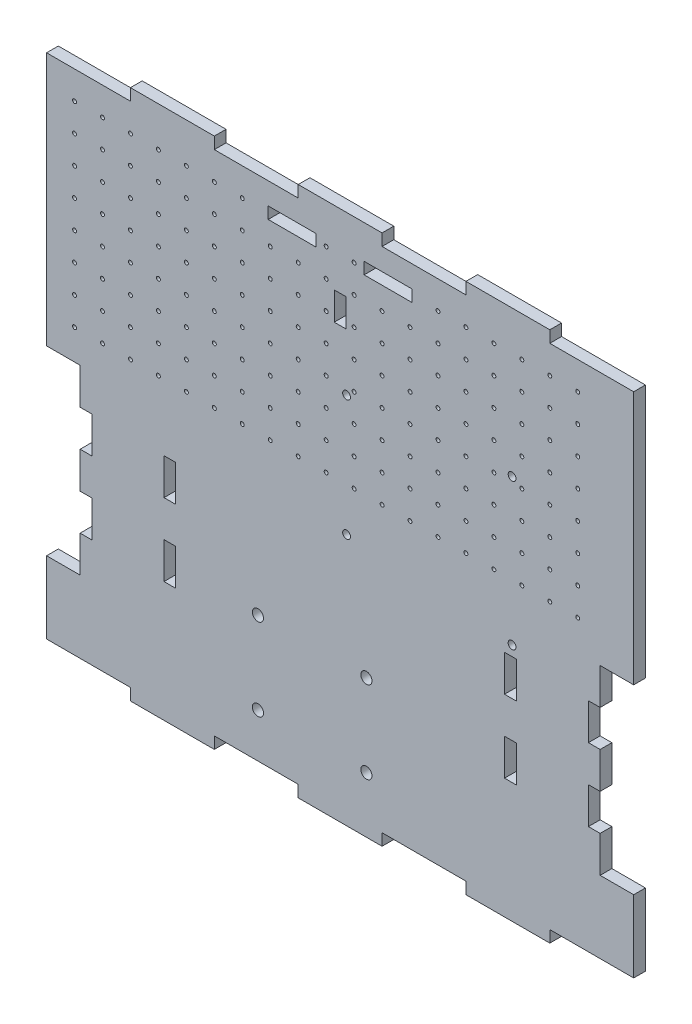
SolidWorks part; units mm, degrees
ref_plane "Front Plane" through (0, 0, 0) normal (0, 0, 1) x (1, 0, 0)
ref_plane "Top Plane" through (0, 0, 0) normal (0, 1, 0) x (1, 0, 0)
ref_plane "Right Plane" through (0, 0, 0) normal (1, 0, 0) x (0, 0, -1)
sketch "Sketch1" plane through (0, 0, 0) normal (0, 0, 1) x (1, 0, 0)
  line L1 (-133.35, 120.65) -> (133.35, 120.65)
  line L2 (-133.35, 120.65) -> (-133.35, -120.65)
  line L3 (-133.35, -120.65) -> (133.35, -120.65)
  line L4 (133.35, 120.65) -> (133.35, -120.65)
  line L5 (-133.35, 120.65) -> (133.35, -120.65) construction
  line L6 (-133.35, -120.65) -> (133.35, 120.65) construction
  point P0 (0, 0)
  dimension "D1" = 241.3
  dimension "D2" = 266.7
extrude "Boss-Extrude1" add sketch "Sketch1" along normal blind 5.334
sketch "Sketch2" plane through (0, 0, 0) normal (0, 0, -1) x (-1, 0, 0)
  line L0 (133.35, 120.65) -> (133.35, -120.65) construction
  line L1 (133.35, 0) -> (118.11, 0)
  line L2 (133.35, 0) -> (133.35, -82.55)
  line L3 (133.35, -82.55) -> (118.11, -82.55)
  line L4 (118.11, 0) -> (118.11, -82.55)
  line L5 (-133.35, -120.65) -> (-133.35, 120.65) construction
  line L6 (-133.35, 0) -> (-118.11, 0)
  line L7 (-133.35, 0) -> (-133.35, -82.55)
  line L8 (-133.35, -82.55) -> (-118.11, -82.55)
  line L9 (-118.11, 0) -> (-118.11, -82.55)
  line L10 (133.35, -120.65) -> (-133.35, -120.65) construction
  dimension "D1" = 82.55
  dimension "D2" = 82.55
  dimension "D3" = 38.1
  dimension "D4" = 38.1
  dimension "D5" = 15.24
  dimension "D6" = 15.24
extrude "Cut-Extrude1" cut sketch "Sketch2" against normal through all
sketch "Sketch9" plane through (0, 0, 5.334) normal (0, 0, 1) x (1, 0, 0)
  line L0 (-118.11, 0) -> (-118.11, -82.55) construction
  line L1 (-118.11, -16.51) -> (-112.776, -16.51)
  line L2 (-118.11, -16.51) -> (-118.11, -33.02)
  line L3 (-118.11, -33.02) -> (-112.776, -33.02)
  line L4 (-112.776, -16.51) -> (-112.776, -33.02)
  line L5 (-118.11, 0) -> (-112.776, 0) construction
  line L6 (-118.11, -49.53) -> (-112.776, -49.53)
  line L7 (-118.11, -49.53) -> (-118.11, -66.04)
  line L8 (-118.11, -66.04) -> (-112.776, -66.04)
  line L9 (-112.776, -49.53) -> (-112.776, -66.04)
  line L10 (-112.776, 0) -> (-112.776, -16.51) construction
  line L11 (-112.776, -33.02) -> (-112.776, -49.53) construction
  line L12 (-118.11, -82.55) -> (-112.776, -82.55) construction
  line L13 (-112.776, -82.55) -> (-112.776, -66.04) construction
  line L14 (0, -120.65) -> (0, 120.65) construction
  line L15 (-133.35, -120.65) -> (133.35, -120.65) construction
  line L16 (133.35, 120.65) -> (-133.35, 120.65) construction
  line L17 (112.776, -82.55) -> (112.776, -66.04) construction
  line L18 (118.11, -82.55) -> (112.776, -82.55) construction
  line L19 (112.776, -33.02) -> (112.776, -49.53) construction
  line L20 (112.776, 0) -> (112.776, -16.51) construction
  line L21 (118.11, 0) -> (112.776, 0) construction
  line L22 (112.776, -49.53) -> (112.776, -66.04)
  line L23 (118.11, -66.04) -> (112.776, -66.04)
  line L24 (118.11, -49.53) -> (118.11, -66.04)
  line L25 (118.11, -49.53) -> (112.776, -49.53)
  line L26 (112.776, -16.51) -> (112.776, -33.02)
  line L27 (118.11, -33.02) -> (112.776, -33.02)
  line L28 (118.11, -16.51) -> (118.11, -33.02)
  line L29 (118.11, -16.51) -> (112.776, -16.51)
  dimension "D1" = 5.334
extrude "Cut-Extrude2" cut sketch "Sketch9" against normal through all
sketch "Sketch10" plane through (0, 0, 5.334) normal (0, 0, 1) x (1, 0, 0)
  line L2 (-133.35, -120.65) -> (133.35, -120.65) construction
  line L3 (-133.35, -82.55) -> (-133.35, -120.65) construction
  circle A0 centre (-37.338, -95.25) radius 2.54
  circle A1 centre (11.938, -95.25) radius 2.54
  circle A2 centre (11.938, -57.912) radius 2.54
  circle A3 centre (-37.338, -57.912) radius 2.54
  dimension "D1" = 96.012
  dimension "D2" = 49.276
  dimension "D3" = 25.4
  dimension "D4" = 2
  dimension "D5" = 2
extrude "Cut-Extrude3" cut sketch "Sketch10" against normal through all
sketch "Sketch19" plane through (0, 0, 5.334) normal (0, 0, 1) x (1, 0, 0)
  line L0 (-10.8958, 100.076) -> (10.8958, 100.076) construction
  line L1 (-32.6875, 105.41) -> (-10.8958, 105.41)
  line L2 (-32.6875, 105.41) -> (-32.6875, 100.076)
  line L3 (-32.6875, 100.076) -> (-10.8958, 100.076)
  line L4 (-10.8958, 105.41) -> (-10.8958, 100.076)
  line L5 (10.8958, 105.41) -> (32.6875, 105.41)
  line L6 (10.8958, 105.41) -> (10.8958, 100.076)
  line L7 (10.8958, 100.076) -> (32.6875, 100.076)
  line L8 (32.6875, 105.41) -> (32.6875, 100.076)
  line L9 (-32.6875, 100.076) -> (-133.35, 100.076) construction
  line L10 (-133.35, 120.65) -> (-133.35, 0) construction
  line L11 (32.6875, 100.076) -> (133.35, 100.076) construction
  line L12 (133.35, 0) -> (133.35, 120.65) construction
  line L13 (133.35, 120.65) -> (-133.35, 120.65) construction
  dimension "D1" = 15.24
  dimension "D2" = 5.334
  dimension "D3" = 5.334
  dimension "D4" = 21.7917
sketch "Sketch23" plane through (0, 0, 5.334) normal (0, 0, 1) x (1, 0, 0)
  line L0 (-112.776, -24.765) -> (-61.976, -24.765) construction
  line L1 (-112.776, -33.02) -> (-112.776, -16.51) construction
  line L2 (-112.776, -16.51) -> (-74.676, -16.51) construction
  line L3 (-112.776, -33.02) -> (-74.676, -33.02) construction
  line L4 (-118.11, -41.275) -> (118.11, -41.275) construction
  line L5 (-118.11, -33.02) -> (-118.11, -49.53) construction
  line L6 (118.11, -49.53) -> (118.11, -33.02) construction
  line L7 (-112.776, -49.53) -> (-74.676, -49.53) construction
  line L8 (-112.776, -57.785) -> (-61.976, -57.785) construction
  line L9 (-112.776, -66.04) -> (-74.676, -66.04) construction
  line L10 (0, -120.65) -> (0, 120.65) construction
  line L11 (-133.35, -120.65) -> (133.35, -120.65) construction
  line L12 (133.35, 120.65) -> (-133.35, 120.65) construction
  line L13 (112.776, -66.04) -> (74.676, -66.04) construction
  line L14 (112.776, -49.53) -> (74.676, -49.53) construction
  line L15 (112.776, -33.02) -> (74.676, -33.02) construction
  line L16 (112.776, -16.51) -> (74.676, -16.51) construction
  line L17 (-74.676, -66.04) -> (-80.01, -66.04)
  line L18 (74.676, -16.51) -> (80.01, -16.51)
  line L19 (74.676, -16.51) -> (74.676, -33.02)
  line L20 (74.676, -33.02) -> (80.01, -33.02)
  line L21 (80.01, -16.51) -> (80.01, -33.02)
  line L22 (74.676, -49.53) -> (80.01, -49.53)
  line L23 (74.676, -49.53) -> (74.676, -66.04)
  line L24 (74.676, -66.04) -> (80.01, -66.04)
  line L25 (80.01, -49.53) -> (80.01, -66.04)
  line L26 (-80.01, -49.53) -> (-80.01, -66.04)
  line L27 (-74.676, -49.53) -> (-74.676, -66.04)
  line L28 (-74.676, -49.53) -> (-80.01, -49.53)
  line L29 (-74.676, -33.02) -> (-80.01, -33.02)
  line L30 (-80.01, -16.51) -> (-80.01, -33.02)
  line L31 (-74.676, -16.51) -> (-80.01, -16.51)
  line L32 (-74.676, -16.51) -> (-74.676, -33.02)
  line L33 (112.776, -16.51) -> (112.776, -33.02) construction
  dimension "D1" = 5.334
  dimension "D2" = 5.334
  dimension "D3" = 32.766
  dimension "D4" = 32.766
extrude "Cut-Extrude8" cut sketch "Sketch23" against normal through all
extrude "Cut-Extrude9" cut sketch "Sketch19" against normal through all contours L1 L4 L3 L2
sketch "Sketch24" plane through (0, 0, 0) normal (0, 0, -1) x (-1, 0, 0)
  line L0 (0, 120.65) -> (0, -120.65) construction
  line L1 (-133.35, 120.65) -> (133.35, 120.65) construction
  line L2 (133.35, -120.65) -> (-133.35, -120.65) construction
extrude "Cut-Extrude11" cut sketch "Sketch19<5>" against normal through all
sketch "Sketch19<5>" plane through (0, 0, 5.334) normal (0, 0, 1) x (1, 0, 0) same geometry as "Sketch19"
sketch "Sketch26" plane through (0, 0, 5.334) normal (0, 0, 1) x (1, 0, 0)
sketch "Sketch27" plane through (0, 0, 5.334) normal (0, 0, 1) x (1, 0, 0)
  line L0 (10.8958, 100.076) -> (32.6875, 100.076) construction
  line L1 (-2.667, 87.376) -> (2.667, 87.376)
  line L2 (-2.667, 87.376) -> (-2.667, 74.676)
  line L3 (-2.667, 74.676) -> (2.667, 74.676)
  line L4 (2.667, 87.376) -> (2.667, 74.676)
  line L9 (133.35, 0) -> (133.35, 120.65) construction
  line L10 (-133.35, 120.65) -> (-133.35, 0) construction
  line L11 (2.667, 74.676) -> (133.35, 74.676) construction
  line L12 (-2.667, 74.676) -> (-133.35, 74.676) construction
  dimension "D1" = 12.7
  dimension "D4" = 12.7
  dimension "D5" = 5.334
extrude "Cut-Extrude12" cut sketch "Sketch27" against normal through all
sketch "Sketch28" plane through (0, 0, 0) normal (0, 0, -1) x (-1, 0, 0)
  line L0 (133.35, -120.65) -> (-133.35, -120.65) construction
  line L1 (-133.35, -120.65) -> (-95.25, -120.65)
  line L2 (-133.35, -120.65) -> (-133.35, -115.316)
  line L3 (-133.35, -115.316) -> (-95.25, -115.316)
  line L4 (-95.25, -120.65) -> (-95.25, -115.316)
  line L5 (-57.15, -120.65) -> (-19.05, -120.65)
  line L6 (-57.15, -120.65) -> (-57.15, -115.316)
  line L7 (-57.15, -115.316) -> (-19.05, -115.316)
  line L8 (-19.05, -120.65) -> (-19.05, -115.316)
  line L9 (133.35, -82.55) -> (133.35, -120.65) construction
  line L10 (19.05, -120.65) -> (57.15, -120.65)
  line L11 (19.05, -120.65) -> (19.05, -115.316)
  line L12 (19.05, -115.316) -> (57.15, -115.316)
  line L13 (57.15, -120.65) -> (57.15, -115.316)
  line L14 (95.25, -120.65) -> (133.35, -120.65)
  line L16 (95.25, -115.316) -> (133.35, -115.316)
  line L17 (133.35, -120.65) -> (133.35, -115.316)
  line L18 (-95.25, -115.316) -> (-57.15, -115.316) construction
  line L19 (-19.05, -115.316) -> (19.05, -115.316) construction
  line L20 (95.25, -115.316) -> (57.15, -115.316) construction
  line L21 (133.35, 120.65) -> (133.35, -115.316) construction
  line L22 (133.35, -115.316) -> (133.5431, -115.1744) construction
  line L41 (95.25, -120.65) -> (95.25, -115.316)
  dimension "D1" = 5.334
extrude "Cut-Extrude13" cut sketch "Sketch28" against normal through all
sketch "Sketch29" plane through (0, 0, 0) normal (0, 0, -1) x (-1, 0, 0)
  line L0 (-133.35, 120.65) -> (133.35, 120.65) construction
  line L1 (-133.35, 120.65) -> (-95.25, 120.65)
  line L2 (-133.35, 120.65) -> (-133.35, 115.316)
  line L3 (-133.35, 115.316) -> (-95.25, 115.316)
  line L4 (-95.25, 120.65) -> (-95.25, 115.316)
  line L5 (-57.15, 120.65) -> (-19.05, 120.65)
  line L6 (-57.15, 120.65) -> (-57.15, 115.316)
  line L7 (-57.15, 115.316) -> (-19.05, 115.316)
  line L8 (-19.05, 120.65) -> (-19.05, 115.316)
  line L9 (133.35, 120.65) -> (133.35, 0) construction
  line L10 (19.05, 120.65) -> (57.15, 120.65)
  line L11 (19.05, 120.65) -> (19.05, 115.316)
  line L12 (19.05, 115.316) -> (57.15, 115.316)
  line L13 (57.15, 120.65) -> (57.15, 115.316)
  line L14 (95.25, 120.65) -> (133.35, 120.65)
  line L15 (95.25, 120.65) -> (95.25, 115.316)
  line L16 (95.25, 115.316) -> (133.35, 115.316)
  line L17 (133.35, 120.65) -> (133.35, 115.316)
  line L18 (-95.25, 115.316) -> (-57.15, 115.316) construction
  line L19 (19.05, 115.316) -> (-19.05, 115.316) construction
  line L20 (57.15, 115.316) -> (95.25, 115.316) construction
  dimension "D1" = 5.334
extrude "Cut-Extrude14" cut sketch "Sketch29" against normal through all
sketch "Sketch30" plane through (0, 0, 5.334) normal (0, 0, 1) x (1, 0, 0)
  line L0 (-95.25, 115.316) -> (-133.35, 115.316) construction
  line L1 (-133.35, 115.316) -> (-133.35, 0) construction
  line L2 (-120.65, 102.616) -> (-107.95, 102.616) construction
  circle A0 centre (-120.65, 102.616) radius 0.889
  circle A1 centre (-107.95, 102.616) radius 0.889
  circle A2 centre (-95.25, 102.616) radius 0.889
  circle A3 centre (-82.55, 102.616) radius 0.889
  circle A4 centre (-69.85, 102.616) radius 0.889
  circle A5 centre (-57.15, 102.616) radius 0.889
  circle A6 centre (-44.45, 102.616) radius 0.889
  circle A7 centre (-31.75, 102.616) radius 0.889 [skipped]
  circle A8 centre (-19.05, 102.616) radius 0.889 [skipped]
  circle A9 centre (-6.35, 102.616) radius 0.889
  circle A10 centre (6.35, 102.616) radius 0.889
  circle A11 centre (19.05, 102.616) radius 0.889 [skipped]
  circle A12 centre (31.75, 102.616) radius 0.889 [skipped]
  circle A13 centre (44.45, 102.616) radius 0.889
  circle A14 centre (57.15, 102.616) radius 0.889
  circle A15 centre (69.85, 102.616) radius 0.889
  circle A16 centre (82.55, 102.616) radius 0.889
  circle A17 centre (95.25, 102.616) radius 0.889
  circle A18 centre (107.95, 102.616) radius 0.889
  circle A19 centre (-107.95, 89.916) radius 0.889
  circle A20 centre (-95.25, 89.916) radius 0.889
  circle A21 centre (-82.55, 89.916) radius 0.889
  circle A22 centre (-69.85, 89.916) radius 0.889
  circle A23 centre (-57.15, 89.916) radius 0.889
  circle A24 centre (-44.45, 89.916) radius 0.889
  circle A25 centre (-31.75, 89.916) radius 0.889
  circle A26 centre (-19.05, 89.916) radius 0.889
  circle A27 centre (-6.35, 89.916) radius 0.889
  circle A28 centre (6.35, 89.916) radius 0.889
  circle A29 centre (19.05, 89.916) radius 0.889
  circle A30 centre (31.75, 89.916) radius 0.889
  circle A31 centre (44.45, 89.916) radius 0.889
  circle A32 centre (57.15, 89.916) radius 0.889
  circle A33 centre (69.85, 89.916) radius 0.889
  circle A34 centre (82.55, 89.916) radius 0.889
  circle A35 centre (95.25, 89.916) radius 0.889
  circle A36 centre (107.95, 89.916) radius 0.889
  circle A37 centre (-107.95, 77.216) radius 0.889
  circle A38 centre (-95.25, 77.216) radius 0.889
  circle A39 centre (-82.55, 77.216) radius 0.889
  circle A40 centre (-69.85, 77.216) radius 0.889
  circle A41 centre (-57.15, 77.216) radius 0.889
  circle A42 centre (-44.45, 77.216) radius 0.889
  circle A43 centre (-31.75, 77.216) radius 0.889
  circle A44 centre (-19.05, 77.216) radius 0.889
  circle A45 centre (-6.35, 77.216) radius 0.889
  circle A46 centre (6.35, 77.216) radius 0.889
  circle A47 centre (19.05, 77.216) radius 0.889
  circle A48 centre (31.75, 77.216) radius 0.889
  circle A49 centre (44.45, 77.216) radius 0.889
  circle A50 centre (57.15, 77.216) radius 0.889
  circle A51 centre (69.85, 77.216) radius 0.889
  circle A52 centre (82.55, 77.216) radius 0.889
  circle A53 centre (95.25, 77.216) radius 0.889
  circle A54 centre (107.95, 77.216) radius 0.889
  circle A55 centre (-107.95, 64.516) radius 0.889
  circle A56 centre (-95.25, 64.516) radius 0.889
  circle A57 centre (-82.55, 64.516) radius 0.889
  circle A58 centre (-69.85, 64.516) radius 0.889
  circle A59 centre (-57.15, 64.516) radius 0.889
  circle A60 centre (-44.45, 64.516) radius 0.889
  circle A61 centre (-31.75, 64.516) radius 0.889
  circle A62 centre (-19.05, 64.516) radius 0.889
  circle A63 centre (-6.35, 64.516) radius 0.889
  circle A64 centre (6.35, 64.516) radius 0.889
  circle A65 centre (19.05, 64.516) radius 0.889
  circle A66 centre (31.75, 64.516) radius 0.889
  circle A67 centre (44.45, 64.516) radius 0.889
  circle A68 centre (57.15, 64.516) radius 0.889
  circle A69 centre (69.85, 64.516) radius 0.889
  circle A70 centre (82.55, 64.516) radius 0.889
  circle A71 centre (95.25, 64.516) radius 0.889
  circle A72 centre (107.95, 64.516) radius 0.889
  circle A73 centre (-107.95, 51.816) radius 0.889
  circle A74 centre (-95.25, 51.816) radius 0.889
  circle A75 centre (-82.55, 51.816) radius 0.889
  circle A76 centre (-69.85, 51.816) radius 0.889
  circle A77 centre (-57.15, 51.816) radius 0.889
  circle A78 centre (-44.45, 51.816) radius 0.889
  circle A79 centre (-31.75, 51.816) radius 0.889
  circle A80 centre (-19.05, 51.816) radius 0.889
  circle A81 centre (-6.35, 51.816) radius 0.889
  circle A82 centre (6.35, 51.816) radius 0.889
  circle A83 centre (19.05, 51.816) radius 0.889
  circle A84 centre (31.75, 51.816) radius 0.889
  circle A85 centre (44.45, 51.816) radius 0.889
  circle A86 centre (57.15, 51.816) radius 0.889
  circle A87 centre (69.85, 51.816) radius 0.889
  circle A88 centre (82.55, 51.816) radius 0.889
  circle A89 centre (95.25, 51.816) radius 0.889
  circle A90 centre (107.95, 51.816) radius 0.889
  circle A91 centre (-107.95, 39.116) radius 0.889
  circle A92 centre (-95.25, 39.116) radius 0.889
  circle A93 centre (-82.55, 39.116) radius 0.889
  circle A94 centre (-69.85, 39.116) radius 0.889
  circle A95 centre (-57.15, 39.116) radius 0.889
  circle A96 centre (-44.45, 39.116) radius 0.889
  circle A97 centre (-31.75, 39.116) radius 0.889
  circle A98 centre (-19.05, 39.116) radius 0.889
  circle A99 centre (-6.35, 39.116) radius 0.889
  circle A100 centre (6.35, 39.116) radius 0.889
  circle A101 centre (19.05, 39.116) radius 0.889
  circle A102 centre (31.75, 39.116) radius 0.889
  circle A103 centre (44.45, 39.116) radius 0.889
  circle A104 centre (57.15, 39.116) radius 0.889
  circle A105 centre (69.85, 39.116) radius 0.889
  circle A106 centre (82.55, 39.116) radius 0.889
  circle A107 centre (95.25, 39.116) radius 0.889
  circle A108 centre (107.95, 39.116) radius 0.889
  circle A109 centre (-107.95, 26.416) radius 0.889
  circle A110 centre (-95.25, 26.416) radius 0.889
  circle A111 centre (-82.55, 26.416) radius 0.889
  circle A112 centre (-69.85, 26.416) radius 0.889
  circle A113 centre (-57.15, 26.416) radius 0.889
  circle A114 centre (-44.45, 26.416) radius 0.889
  circle A115 centre (-31.75, 26.416) radius 0.889
  circle A116 centre (-19.05, 26.416) radius 0.889
  circle A117 centre (-6.35, 26.416) radius 0.889
  circle A118 centre (6.35, 26.416) radius 0.889
  circle A119 centre (19.05, 26.416) radius 0.889
  circle A120 centre (31.75, 26.416) radius 0.889
  circle A121 centre (44.45, 26.416) radius 0.889
  circle A122 centre (57.15, 26.416) radius 0.889
  circle A123 centre (69.85, 26.416) radius 0.889
  circle A124 centre (82.55, 26.416) radius 0.889
  circle A125 centre (95.25, 26.416) radius 0.889
  circle A126 centre (107.95, 26.416) radius 0.889
  circle A127 centre (-107.95, 13.716) radius 0.889
  circle A128 centre (-95.25, 13.716) radius 0.889
  circle A129 centre (-82.55, 13.716) radius 0.889
  circle A130 centre (-69.85, 13.716) radius 0.889
  circle A131 centre (-57.15, 13.716) radius 0.889
  circle A132 centre (-44.45, 13.716) radius 0.889
  circle A133 centre (-31.75, 13.716) radius 0.889
  circle A134 centre (-19.05, 13.716) radius 0.889
  circle A135 centre (-6.35, 13.716) radius 0.889
  circle A136 centre (6.35, 13.716) radius 0.889
  circle A137 centre (19.05, 13.716) radius 0.889
  circle A138 centre (31.75, 13.716) radius 0.889
  circle A139 centre (44.45, 13.716) radius 0.889
  circle A140 centre (57.15, 13.716) radius 0.889
  circle A141 centre (69.85, 13.716) radius 0.889
  circle A142 centre (82.55, 13.716) radius 0.889
  circle A143 centre (95.25, 13.716) radius 0.889
  circle A144 centre (107.95, 13.716) radius 0.889
  circle A145 centre (-120.65, 89.916) radius 0.889
  circle A146 centre (-120.65, 77.216) radius 0.889
  circle A147 centre (-120.65, 64.516) radius 0.889
  circle A148 centre (-120.65, 51.816) radius 0.889
  circle A149 centre (-120.65, 39.116) radius 0.889
  circle A150 centre (-120.65, 26.416) radius 0.889
  circle A151 centre (-120.65, 13.716) radius 0.889
  dimension "D1" = 1.778
  dimension "D2" = 12.7
  dimension "D3" = 12.7
  dimension "D6" = 12.7
  dimension "D4" = 19
  dimension "D5" = 8
extrude "Cut-Extrude15" cut sketch "Sketch30" against normal through all
sketch "Sketch32" plane through (0, 0, 0) normal (0, 0, -1) x (-1, 0, 0)
  circle A0 centre (-78.105, -11.938) radius 1.778 construction
  circle A1 centre (-2.921, -6.096) radius 1.778 construction
  circle A2 centre (-78.105, 54.356) radius 1.778 construction
  circle A3 centre (-2.921, 48.768) radius 1.778 construction
  circle A4 centre (-78.105, -11.938) radius 1.778
  circle A5 centre (-2.921, -6.096) radius 1.778
  circle A6 centre (-78.105, 54.356) radius 1.778
  circle A7 centre (-2.921, 48.768) radius 1.778
extrude "Cut-Extrude16" cut sketch "Sketch32" against normal through all
equation "\"MDF\"= .21in"
equation "\"Foamcore\"= .13in"
equation "\"Gmaterial\"= \"MDF\""
equation "\"D1@Sketch9\"=\"MDF\""
equation "\"D2@Sketch19\"=\"MDF\""
equation "\"D3@Sketch19\"=\"MDF\""
equation "\"D1@Sketch23\"=\"MDF\""
equation "\"D2@Sketch23\"=\"D1@Sketch23\""
equation "\"D1@Boss-Extrude1\"=\"MDF\""
equation "\"D3@Sketch23\"=1.29"
equation "\"D5@Sketch27\"=\"MDF\""
equation "\"D1@Sketch28\"=\"MDF\""
equation "\"D1@Sketch29\"=\"MDF\""
